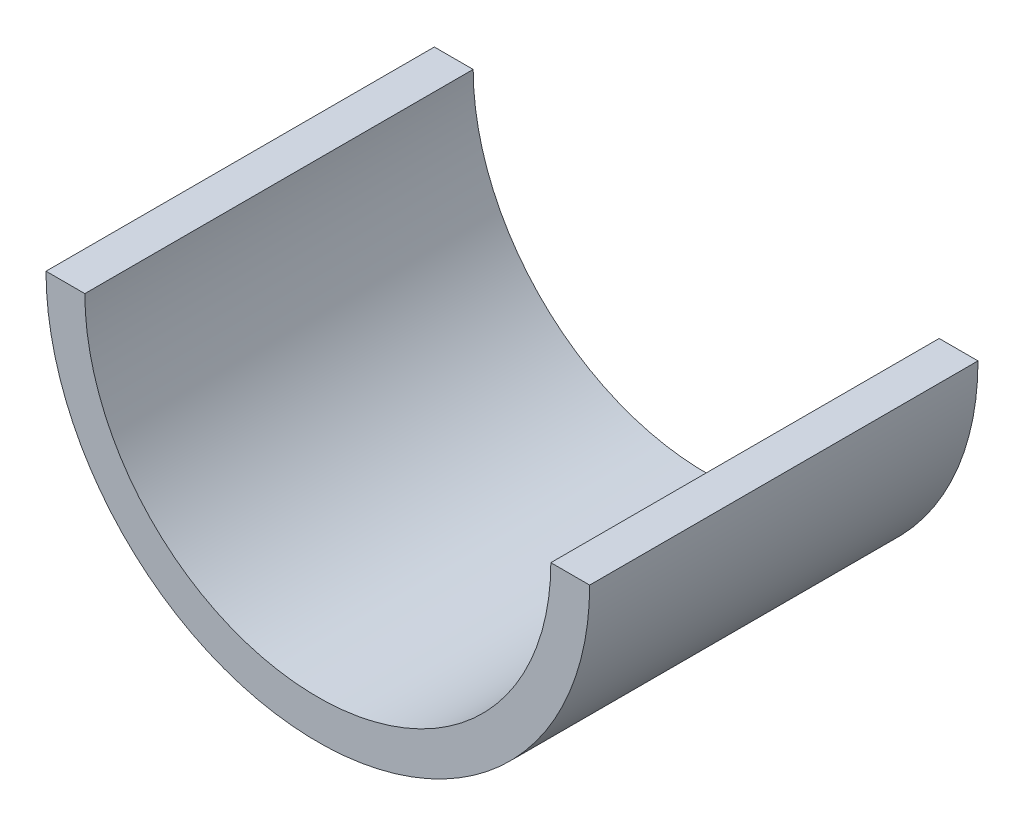
SolidWorks part; units mm, degrees
ref_plane "Спереди" through (0, 0, 0) normal (0, 0, 1) x (1, 0, 0)
ref_plane "Сверху" through (0, 0, 0) normal (0, 1, 0) x (1, 0, 0)
ref_plane "Справа" through (0, 0, 0) normal (1, 0, 0) x (0, 0, -1)
other "Configuration Table"
sketch "Эскиз1" plane through (0, 0, 0) normal (0, 0, 1) x (1, 0, 0)
  line L0 (-35, 0) -> (35, 0)
  arc A0 (-30, 0) -> (30, 0) centre (0, 0) ccw
  arc A1 (-35, 0) -> (35, 0) centre (0, 0) ccw
  circle A2 centre (0, 0) radius 35 construction
  circle A3 centre (0, 0) radius 30 construction
  dimension "D1" = 60
  dimension "D2" = 5
extrude "Бобышка-Вытянуть1" add sketch "Эскиз1" along normal blind 50 contours L0 A1 A0 region at (-32.5, -0.7826, 0)
